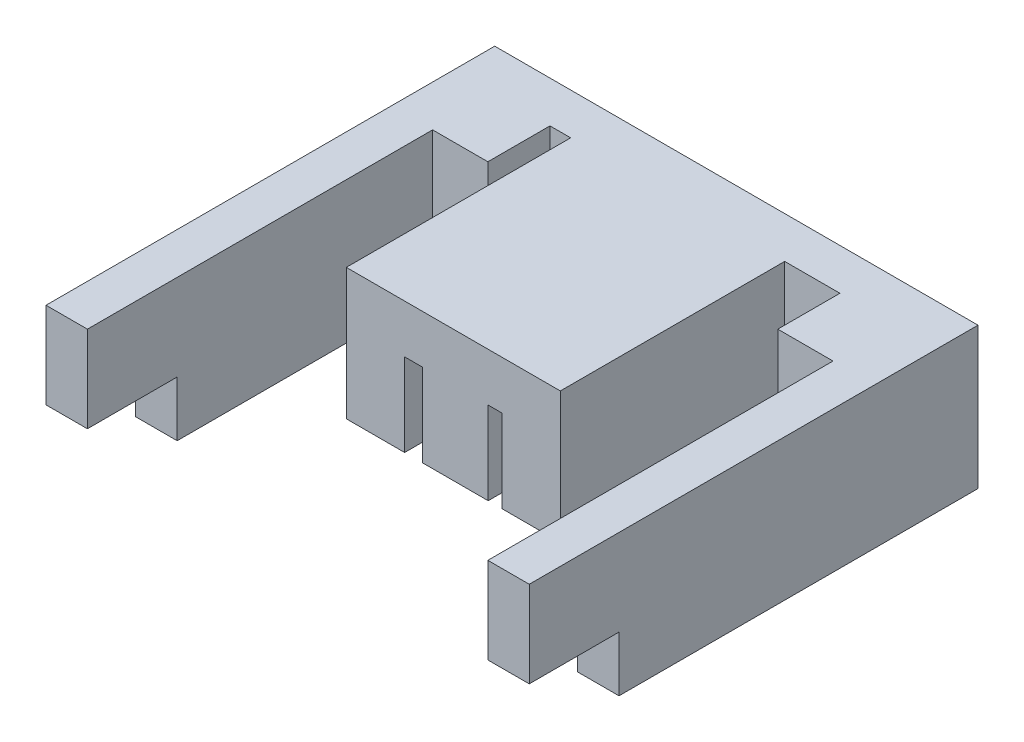
SolidWorks part; units mm, degrees
material "PBT General Purpose"
ref_plane "Front Plane" through (0, 0, 0) normal (0, 0, 1) x (1, 0, 0)
ref_plane "Top Plane" through (0, 0, 0) normal (0, 1, 0) x (1, 0, 0)
ref_plane "Right Plane" through (0, 0, 0) normal (1, 0, 0) x (0, 0, -1)
sketch "Sketch1" plane through (0, 0, 0) normal (0, 1, 0) x (1, 0, 0)
  line L0 (29, -32.5) -> (35, -32.5)
  line L1 (-35, 32.5) -> (35, 32.5)
  line L2 (-35, 32.5) -> (-35, -32.5)
  line L3 (-35, -32.5) -> (-29, -32.5)
  line L4 (35, 32.5) -> (35, -32.5)
  line L5 (-29, 26.5) -> (29, 26.5)
  line L6 (-29, 26.5) -> (-29, -32.5)
  line L8 (29, 26.5) -> (29, -32.5)
  point P8 (0, 26.5)
  point P10 (-35, 0)
  dimension "D1" = 70
  dimension "D2" = 65
  dimension "D3" = 6
  dimension "D4" = 6
  dimension "D5" = 6
extrude "Boss-Extrude1" add sketch "Sketch1" along normal blind 20.5
sketch "Sketch2" plane through (0, 0, 0) normal (0, -1, 0) x (1, 0, 0)
  line L0 (35, 32.5) -> (35, -32.5) construction
  line L1 (29, 32.5) -> (35, 32.5)
  line L2 (29, 32.5) -> (29, 19.5)
  line L3 (29, 19.5) -> (35, 19.5)
  line L4 (35, 32.5) -> (35, 19.5)
  line L5 (0, -1000) -> (0, 49000) construction
  line L6 (-29, -26.5) -> (29, -26.5) construction
  line L7 (-12.5, -26.5) -> (12.5, -26.5)
  line L8 (-12.5, -26.5) -> (-12.5, -32.5)
  line L9 (-12.5, -32.5) -> (12.5, -32.5)
  line L10 (12.5, -26.5) -> (12.5, -32.5)
  line L11 (35, -32.5) -> (-35, -32.5) construction
  line L12 (-29, 19.5) -> (-35, 19.5)
  line L13 (-35, 32.5) -> (-35, 19.5)
  line L14 (-29, 32.5) -> (-35, 32.5)
  line L15 (-29, 32.5) -> (-29, 19.5)
  point P18 (0, -26.5)
  point P19 (0, -26.5)
  dimension "D1" = 13
  dimension "D2" = 25
extrude "Cut-Extrude1" cut sketch "Sketch2" against normal blind 8
sketch "Sketch3" plane through (0, 20.5, 0) normal (0, 1, 0) x (1, 0, 0)
  line L0 (-29, -32.5) -> (-29, 26.5) construction
  line L1 (-14, 21) -> (9, 21)
  line L2 (-14, 21) -> (-14, -2)
  line L3 (-14, -2) -> (9, -2)
  line L4 (9, 21) -> (9, -2)
  line L5 (-29, 26.5) -> (29, 26.5) construction
  dimension "D1" = 23
  dimension "D2" = 23
  dimension "D3" = 15
  dimension "D4" = 5.5
extrude "Boss-Extrude2" add sketch "Sketch3" against normal offset from surface (7 mm away) 13.5 separate body up to face at (-25.5, 0, -13.1667)
sketch "Sketch4" plane through (0, 20.5, 0) normal (0, 1, 0) x (1, 0, 0)
  line L0 (-18, 26.5) -> (-18, -6)
  line L1 (-29, 26.5) -> (29, 26.5) construction
  line L2 (-18, -6) -> (13, -6)
  line L3 (13, -6) -> (13, 26.5)
  line L4 (-14, 21) -> (-14, -2)
  line L5 (-14, -2) -> (9, -2)
  line L6 (9, -2) -> (9, 21)
  line L7 (9, 21) -> (-14, 21)
  line L8 (-14, 21) -> (-14, -2)
  line L9 (-14, -2) -> (9, -2)
  line L10 (9, -2) -> (9, 21)
  line L11 (9, 21) -> (-14, 21)
  line L12 (13, 26.5) -> (-18, 26.5)
  line M12 (-29, 26.5) -> (29, 26.5)
  dimension "D2" = 4
  dimension "D3" = 4
  dimension "D4" = 4
  dimension "D1" = 0
extrude "Boss-Extrude4" add sketch "Sketch4" against normal offset from surface (19 mm away) 12 contours L2 L3 L0 L11 L10 L9 L8 M12 region at (-2.5, 20.5, -26.0509) up to face at (-2.5, 13.5, -9.5) offset beyond the face yes
sketch "Sketch5" plane through (0, 1.5, 0) normal (0, -1, 0) x (1, 0, 0)
  line L0 (-14, -21) -> (9, -21) construction
  line L1 (-6.95, -21) -> (-9.55, -21)
  line L2 (-6.95, -21) -> (-6.95, -26.5)
  line L3 (-6.95, -26.5) -> (-9.55, -26.5)
  line L4 (-9.55, -21) -> (-9.55, -26.5)
  line L5 (12.5, -26.5) -> (-12.5, -26.5) construction
  line L6 (9, 2) -> (-14, 2) construction
  line L7 (-9.55, 2) -> (-6.95, 2)
  line L8 (-9.55, 2) -> (-9.55, 6)
  line L9 (-9.55, 6) -> (-6.95, 6)
  line L10 (-6.95, 2) -> (-6.95, 6)
  line L11 (13, 6) -> (-18, 6) construction
  line L12 (-18, 6) -> (-18, -26.5) construction
  line L13 (-18, 2) -> (-14, 2)
  line L14 (-18, 2) -> (-18, -13)
  line L15 (-18, -13) -> (-14, -13)
  line L16 (-14, 2) -> (-14, -13)
  line L17 (-14, 2) -> (-14, -21) construction
  line L18 (9, 2) -> (-14, 2) construction
  line L19 (2.55, 6) -> (4.55, 6)
  line L20 (2.55, 6) -> (2.55, 2)
  line L21 (2.55, 2) -> (4.55, 2)
  line L22 (4.55, 6) -> (4.55, 2)
  line L23 (-14, 2) -> (-14, -21) construction
  dimension "D1" = 2
  dimension "D2" = 9.5
  dimension "D3" = 15
  dimension "D4" = 2.6
  dimension "D5" = 4.45
extrude "Cut-Extrude2" cut sketch "Sketch5" against normal up to surface (12 mm away) up to face at (-2.5, 13.5, -9.5)
sketch "Sketch6" plane through (0, 0, 0) normal (0, -1, 0) x (1, 0, 0)
  line L1 (-35, 19.5) -> (-29, 19.5) construction
  line L2 (-29, -26.5) -> (-12.5, -26.5) construction
  circle A0 centre (-32, 14.5) radius 1.5
  circle A1 centre (-32, -21.5) radius 1.5
  point P6 (-32, 19.5)
  dimension "D1" = 3
  dimension "D3" = 3
  dimension "D2" = 5
  dimension "D4" = 5
extrude "Cut-Extrude3" cut sketch "Sketch6" against normal blind 10
mirror "Mirror1" about plane through (0, 0, 0) normal (1, 0, 0) of "Cut-Extrude3"
sketch "Sketch7" plane through (0, 20.5, 0) normal (0, 1, 0) x (1, 0, 0)
  line L1 (29, 26.5) -> (21, 26.5)
  line L2 (29, 26.5) -> (29, 17.5)
  line L3 (29, 17.5) -> (21, 17.5)
  line L4 (21, 26.5) -> (21, 17.5)
  line L5 (-29, 26.5) -> (-21, 26.5)
  line L6 (-29, 26.5) -> (-29, 17.5)
  line L7 (-29, 17.5) -> (-21, 17.5)
  line L8 (-21, 26.5) -> (-21, 17.5)
  dimension "D1" = 8
  dimension "D2" = 9
  dimension "D3" = 9
  dimension "D4" = 8
extrude "Boss-Extrude5" add sketch "Sketch7" against normal up to surface (20.5 mm away) up to face at (32, 0, 13)
sketch "Sketch8" plane through (0, 0, -32.5) normal (0, 0, -1) x (-1, 0, 0)
  line L0 (-35, 20.5) -> (-35, 0) construction
  line L1 (35, 20.5) -> (35, 0) construction
  line L2 (12.5, 0) -> (35, 0) construction
  line L3 (-35, 0) -> (-12.5, 0) construction
  circle A0 centre (-25, 11) radius 2
  circle A1 centre (25, 11) radius 2
  dimension "D1" = 4
  dimension "D2" = 4
  dimension "D5" = 11
  dimension "D6" = 11
  dimension "D3" = 10
  dimension "D4" = 10
extrude "Cut-Extrude4" cut sketch "Sketch8" against normal blind 10
equation "\"body_height\"= 41mm"
equation "\"D1@Boss-Extrude1\"=\"body_height\" / 2"
equation "\"D1@Boss-Extrude2\"=12+1.5"
